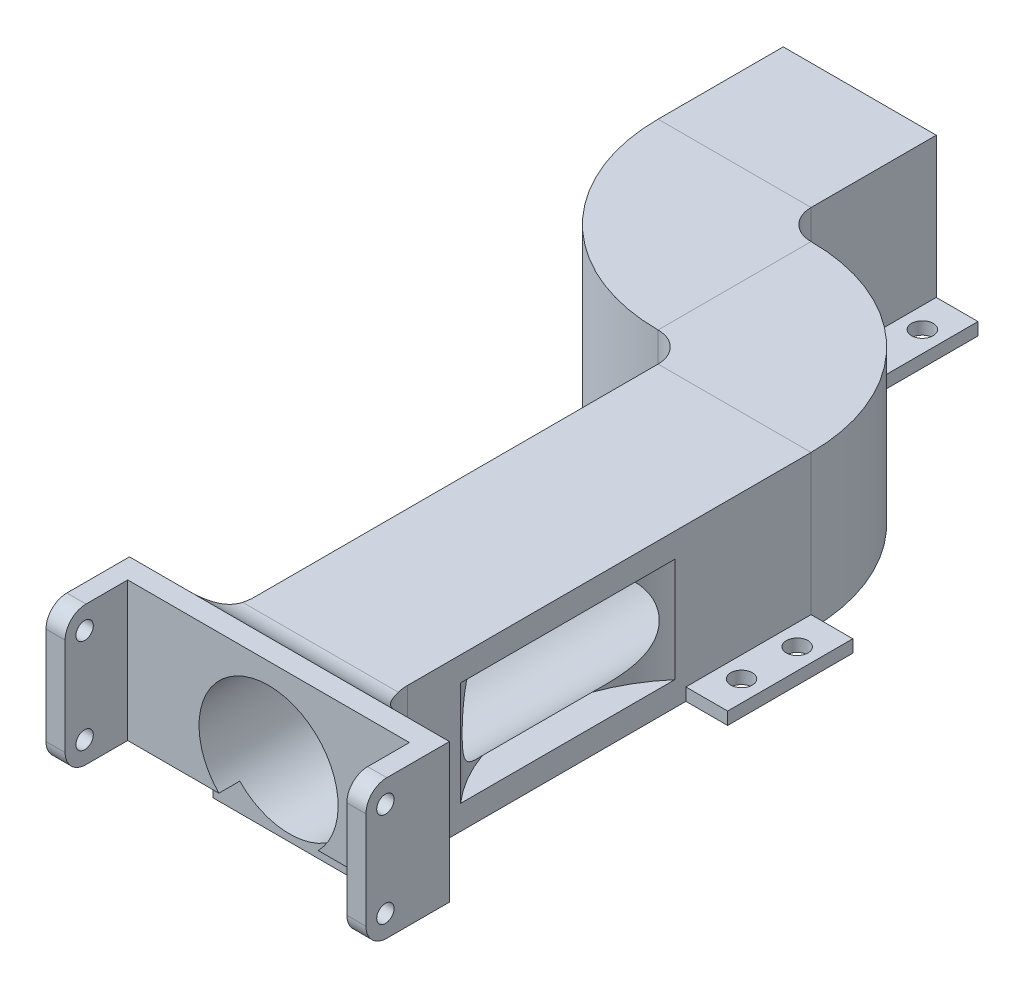
SolidWorks part; units mm, degrees
ref_plane "Front Plane" through (0, 0, 0) normal (0, 0, 1) x (1, 0, 0)
ref_plane "Top Plane" through (0, 0, 0) normal (0, 1, 0) x (1, 0, 0)
ref_plane "Right Plane" through (0, 0, 0) normal (1, 0, 0) x (0, 0, -1)
sketch "Sketch1" plane through (0, 0, 0) normal (0, 0, 1) x (1, 0, 0)
  line L0 (55, 0) -> (-55, 0) construction
  line L1 (-41.5, 11) -> (-19.5, 11)
  line L2 (-41.5, 11) -> (-41.5, -11)
  line L3 (-41.5, -11) -> (-19.5, -11)
  line L4 (-19.5, 11) -> (-19.5, -11)
  line L5 (-41.5, 11) -> (-19.5, -11) construction
  line L6 (-41.5, -11) -> (-19.5, 11) construction
  line L7 (0, -55) -> (0, 55) construction
  point P0 (-30.5, 0)
  dimension "D1" = 22
  dimension "D2" = 22
  dimension "D3" = 30.5
sketch "Sketch2" plane through (0, 0, 0) normal (0, 1, 0) x (1, 0, 0)
  line L0 (-30.5, 0) -> (-30.5, -18)
  line L1 (0, -48.5) -> (0, -66.5)
  line L2 (-55, 0) -> (55, 0) construction
  arc A0 (-30.5, -18) -> (-15.25, -33.25) centre (-15.25, -18) ccw
  arc A1 (0, -48.5) -> (-15.25, -33.25) centre (-15.25, -48.5) ccw
  dimension "D5" = 30.5
  dimension "D3" = 15.25
  dimension "D4" = 30.5
  dimension "D1" = 18
  dimension "D2" = 18
  dimension "D6" = 18
sweep "Sweep1" add profiles "Sketch1" path "Sketch2"
sketch "Sketch3" plane through (0, 0, 66.5) normal (0, 0, 1) x (1, 0, 0)
  circle A0 centre (0, 0) radius 10
  dimension "D1" = 20
sweep "Cut-Sweep1" cut profiles "Sketch3" path "Sketch2<3>"
sketch "Sketch2<3>" plane through (0, 0, 0) normal (0, 1, 0) x (1, 0, 0) same geometry as "Sketch2"
sketch "Sketch6" plane through (0, -11, 0) normal (0, 1, 0) x (1, 0, 0)
  line L0 (-13.4019, 0) -> (13.4019, 0) construction
  line L1 (-13.5, 0) -> (-47.5, 0)
  line L2 (-13.5, 0) -> (-13.5, -18)
  line L3 (-13.5, -18) -> (-47.5, -18)
  line L4 (-47.5, 0) -> (-47.5, -18)
  line L5 (-19.5, 0) -> (-19.5, -18) construction
  line L6 (-11, -48.5) -> (-11, -66.5) construction
  line L7 (-17, -48.5) -> (17, -48.5)
  line L8 (-17, -48.5) -> (-17, -66.5)
  line L9 (-17, -66.5) -> (17, -66.5)
  line L10 (17, -48.5) -> (17, -66.5)
  line L11 (11, -66.5) -> (-11, -66.5) construction
  dimension "D1" = 18
  dimension "D6" = 18
  dimension "D2" = 34
  dimension "D3" = 6
  dimension "D4" = 34
  dimension "D5" = 6
  dimension "D7" = 0
extrude "Boss-Extrude1" add sketch "Sketch6" along normal blind 1.8
sketch "Sketch7" plane through (0, -9.2, 0) normal (0, 1, 0) x (-1, 0, 0)
  line L0 (13.4019, 0) -> (-13.4019, 0) construction
  line L1 (47.5, 0) -> (47.5, 18) construction
  line L2 (13.5, 18) -> (13.5, 0) construction
  line L3 (17, 48.5) -> (17, 66.5) construction
  line L4 (11, 66.5) -> (17, 66.5) construction
  line L5 (-17, 66.5) -> (-17, 48.5) construction
  circle A1 centre (44.5, 5) radius 1.55
  circle A4 centre (14, 61.5) radius 1.55
  circle A6 centre (16.5, 5) radius 1.55
  circle A7 centre (16.5, 13) radius 1.55
  circle A8 centre (44.5, 13) radius 1.55
  circle A9 centre (-14, 61.5) radius 1.55
  circle A10 centre (-14, 53.5) radius 1.55
  circle A11 centre (14, 53.5) radius 1.55
  dimension "D2" = 3.1
  dimension "D8" = 3.1
  dimension "D1" = 5
  dimension "D3" = 3
  dimension "D6" = 3
  dimension "D7" = 8
  dimension "D9" = 3
  dimension "D10" = 5
  dimension "D13" = 3
  dimension "D5" = 2
  dimension "D11" = 2
  dimension "D12" = 2
extrude "Cut-Extrude1" cut sketch "Sketch7" against normal blind 1.8
sketch "Sketch8" plane through (0, 0, 0) normal (0, 0, -1) x (-1, 0, 0)
  line L1 (19.5, 11) -> (41.5, 11)
  line L2 (19.5, 11) -> (19.5, -11)
  line L3 (19.5, -11) -> (41.5, -11)
  line L4 (41.5, 11) -> (41.5, -11)
  line L5 (19.5, 11) -> (41.5, -11) construction
  line L6 (19.5, -11) -> (41.5, 11) construction
  point P0 (30.5, 0)
  dimension "D1" = 22
  dimension "D2" = 22
sketch "Sketch12" plane through (0, 0, 66.5) normal (0, 0, 1) x (1, 0, 0)
  line L1 (-11, 11) -> (11, 11)
  line L2 (-11, 11) -> (-11, -11)
  line L3 (-11, -11) -> (11, -11)
  line L4 (11, 11) -> (11, -11)
extrude "Boss-Extrude3" add sketch "Sketch12" along normal blind 46
sketch "Sketch14" plane through (0, 0, 112.5) normal (0, 0, 1) x (1, 0, 0)
  circle A0 centre (0, 0) radius 10
  dimension "D1" = 20
extrude "Cut-Extrude4" cut sketch "Sketch14" against normal blind 45.5
sketch "Sketch16" plane through (0, 0, 0) normal (0, 1, 0) x (1, 0, 0)
  line L1 (0, -12.1) -> (0, 12.1) construction
  line L2 (-11, -68.0991) -> (-28.75, -83.5)
  line L3 (-11, -48.5) -> (-11, -112.5) construction
  line L4 (-28.75, -83.5) -> (-11, -98.9009)
  line L5 (28.75, -83.5) -> (11, -98.9009)
  line L6 (11, -68.0991) -> (28.75, -83.5)
  line L7 (-17, -66.5) -> (-11, -66.5) construction
  arc A0 (-11, -98.9009) -> (-11, -68.0991) centre (-28.75, -83.5) ccw
  arc A1 (11, -98.9009) -> (11, -68.0991) centre (28.75, -83.5) cw
  point P0 (-28.75, -83.5)
  dimension "D3" = 47
  dimension "D1" = 17
  dimension "D2" = 28.75
extrude "Cut-Extrude5" cut sketch "Sketch16" against normal mid plane 15
sketch "Sketch21" plane through (0, 0, 112.5) normal (0, 0, 1) x (1, 0, 0)
  line L0 (11, -11) -> (17, -11) construction
  line L1 (-23, 13) -> (23, 13)
  line L2 (-23, 13) -> (-23, -7)
  line L3 (-23, -7) -> (23, -7)
  line L4 (23, 13) -> (23, -7)
  line L5 (0, -12.1) -> (0, 12.1) construction
  dimension "D1" = 4
  dimension "D2" = 20
  dimension "D3" = 46
  dimension "D4" = 23
extrude "Boss-Extrude5" add sketch "Sketch21" along normal blind 12
sketch "Sketch22" plane through (0, 0, 124.5) normal (0, 0, 1) x (1, 0, 0)
  line L0 (23, 13) -> (-23, 13) construction
  line L1 (-20.25, 13) -> (20.25, 13)
  line L2 (-20.25, 13) -> (-20.25, -7)
  line L3 (-20.25, -7) -> (20.25, -7)
  line L4 (20.25, 13) -> (20.25, -7)
  line L5 (-23, -7) -> (23, -7) construction
  line L6 (0, -12.1) -> (0, 12.1) construction
  dimension "D1" = 40.5
  dimension "D2" = 20.25
extrude "Cut-Extrude8" cut sketch "Sketch22" against normal blind 9
sketch "Sketch23" plane through (0, 13, 0) normal (0, 1, 0) x (1, 0, 0)
  line L0 (-20.25, -115.5) -> (-23, -115.5) construction
  line L1 (-23, -124.5) -> (-23, -112.5) construction
sketch "Sketch24" plane through (-23, 0, 0) normal (-1, 0, 0) x (0, 0, 1)
  line L0 (124.5, 13) -> (112.5, 13) construction
  line L2 (112.5, 13) -> (112.5, -7) construction
  circle A0 centre (121.7, 9.8) radius 1.25
  circle A1 centre (121.7, -3.8) radius 1.25
  dimension "D3" = 2.5
  dimension "D4" = 2.5
  dimension "D1" = 3.2
  dimension "D5" = 13.6
  dimension "D2" = 9.2
  dimension "D6" = 0
extrude "Cut-Extrude9" cut sketch "Sketch24" against normal blind 50
fillet "Fillet1" radius 3 4 edges at (21.625, -7, 124.5) (21.625, 13, 124.5) (-21.625, -7, 124.5) (-21.625, 13, 124.5)
sketch "Sketch25" plane through (0, 0, 112.5) normal (0, 0, 1) x (1, 0, 0)
  circle A0 centre (0, 0) radius 10
  dimension "D1" = 20
extrude "Cut-Extrude10" cut sketch "Sketch25" along normal blind 9
fillet "Fillet2" radius 6 3 edges at (0, 11, 112.5) (11, 2, 112.5) (-11, 2, 112.5)
sketch "Sketch26" plane through (0, 0, 67) normal (0, 0, 1) x (1, 0, 0)
  circle A0 centre (0, 0) radius 10
extrude "Cut-Extrude11" cut sketch "Sketch26" against normal blind 19
equation "\"D2@Sketch2\"=\"D1@Sketch2\""
equation "\"D6@Sketch2\"=\"D2@Sketch2\""
equation "\"D1@Sketch6\"=18"
equation "\"D8@Sketch7\"=\"D2@Sketch7\""
equation "\"D4@Sketch24\"=\"D3@Sketch24\""
